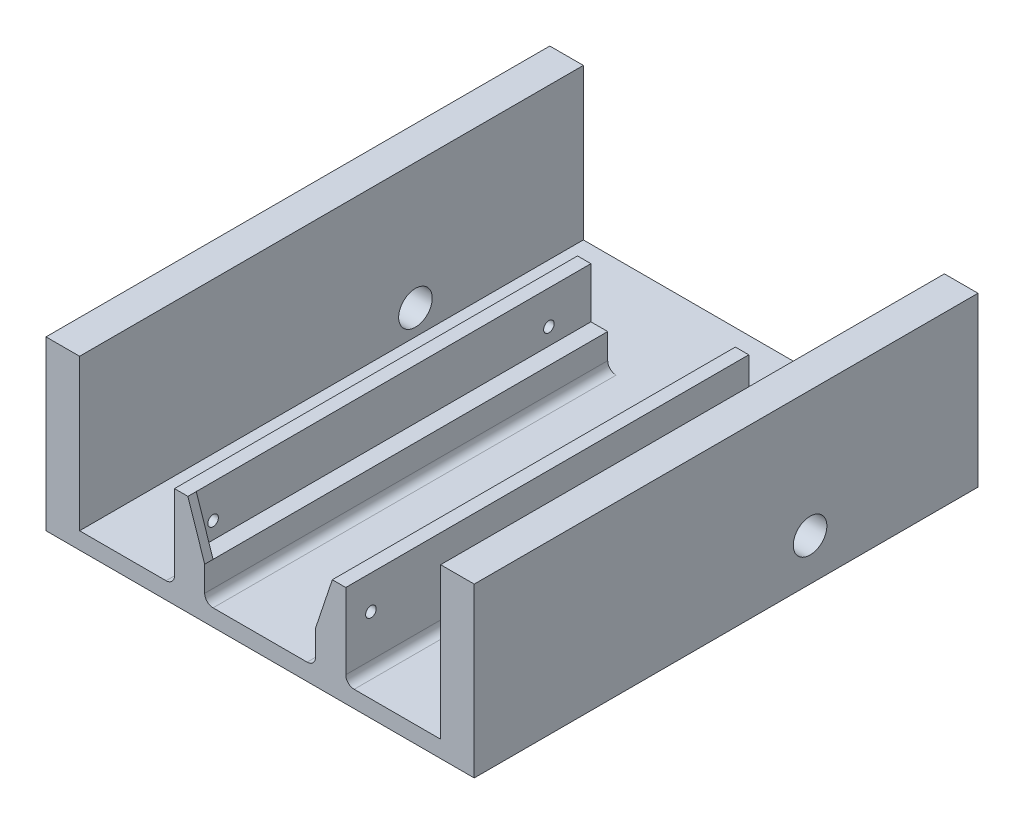
SolidWorks part; units mm, degrees
ref_plane "前基準面" through (0, 0, 0) normal (0, 0, 1) x (1, 0, 0)
ref_plane "上基準面" through (0, 0, 0) normal (0, 1, 0) x (1, 0, 0)
ref_plane "右基準面" through (0, 0, 0) normal (1, 0, 0) x (0, 0, -1)
sketch "草圖4" plane through (0, 0, 0) normal (0, 1, 0) x (1, 0, 0)
  line L1 (-127.5, 150) -> (127.5, 150)
  line L2 (-127.5, 150) -> (-127.5, -150)
  line L3 (-127.5, -150) -> (127.5, -150)
  line L4 (127.5, 150) -> (127.5, -150)
  line L5 (-127.5, 150) -> (127.5, -150) construction
  line L6 (-127.5, -150) -> (127.5, 150) construction
  point P0 (0, 0)
  dimension "D1" = 255
  dimension "D2" = 300
extrude "填料-伸長2" add sketch "草圖4" along normal blind 10
sketch "草圖7" plane through (0, 10, 0) normal (0, 1, 0) x (1, 0, 0)
  line L0 (-127.5, -150) -> (127.5, -150) construction
  line L1 (-127.5, 150) -> (-107.5, 150)
  line L2 (-127.5, 150) -> (-127.5, -150)
  line L3 (-127.5, -150) -> (-107.5, -150)
  line L4 (-107.5, 150) -> (-107.5, -150)
  line L5 (127.5, 150) -> (-127.5, 150) construction
  line L6 (127.5, -150) -> (107.5, -150)
  line L7 (127.5, -150) -> (127.5, 150)
  line L8 (127.5, 150) -> (107.5, 150)
  line L9 (107.5, -150) -> (107.5, 150)
  line L10 (0, 160.1697) -> (0, -166.2631) construction
  line L20 (42.5, -150) -> (-42.5, -150) construction
  line L21 (42.5, -150) -> (42.5, 110) construction
  line L22 (42.5, 110) -> (-42.5, 110) construction
  line L23 (-42.5, -150) -> (-42.5, 110) construction
  dimension "D1" = 20
  dimension "D2" = 20
  dimension "D4" = 260
  dimension "D5" = 85
extrude "填料-伸長3" add sketch "草圖7" along normal blind 90
sketch "草圖8" plane through (0, 0, 150) normal (0, 0, 1) x (1, 0, 0)
  line L0 (0, 114.0362) -> (0, -18.6102) construction
  line L1 (-33, 10) -> (-51, 10)
  line L2 (-107.5, 10) -> (107.5, 10) construction
  line L3 (-51, 10) -> (-51, 60)
  line L4 (-51, 60) -> (-43, 60)
  line L5 (-43, 60) -> (-43, 30)
  line L6 (-43, 30) -> (-33, 30)
  line L7 (-33, 30) -> (-33, 10)
  line L8 (43, 30) -> (33, 30)
  line L9 (43, 60) -> (43, 30)
  line L10 (51, 60) -> (43, 60)
  line L11 (51, 10) -> (51, 60)
  line L12 (33, 10) -> (51, 10)
  line L13 (33, 30) -> (33, 10)
  dimension "D1" = 43
  dimension "D2" = 8
  dimension "D3" = 10
  dimension "D4" = 20
  dimension "D5" = 50
  dimension "D6" = 66
extrude "填料-伸長4" add sketch "草圖8" against normal blind 240
sketch "草圖9" plane through (-127.5, 0, 0) normal (-1, 0, 0) x (0, 0, 1)
  line L0 (-150, 0) -> (150, 0) construction
  line L2 (-150, 100) -> (-150, 0) construction
  circle A0 centre (-50, 25) radius 10
  point P2 (-68.9466, 38.9013)
  point P5 (0, 0)
  point P7 (-150, 25.112)
  point P8 (-80.0453, -19.6192)
  dimension "D1" = 20
  dimension "D2" = 25
  dimension "D3" = 100
extrude "除料-伸長1" cut sketch "草圖9" against normal up to next
mirror "鏡射1" about plane through (0, 0, 0) normal (1, 0, 0) of "除料-伸長1"
sketch "草圖11" plane through (0, 0, 150) normal (0, 0, 1) x (1, 0, 0)
  line L0 (-43, 60) -> (-33, 30)
  line L1 (-51, 60) -> (-43, 60)
  line L2 (-51, 60) -> (-51, 10)
  line L3 (-51, 10) -> (-33, 10)
  line L4 (-33, 30) -> (-33, 10)
  line L5 (33, 10) -> (51, 10)
  line L6 (33, 10) -> (33, 30)
  line L7 (43, 60) -> (51, 60)
  line L8 (51, 10) -> (51, 60)
  line L9 (33, 30) -> (43, 60)
extrude "填料-伸長6" add sketch "草圖11" against normal blind 5
fillet "圓角1" radius 5 4 edges at (51, 10, 30) (-51, 10, 30) (33, 10, 30) (-33, 10, 30)
sketch "草圖12" plane through (51, 0, 0) normal (1, 0, 0) x (0, 0, -1)
  line L0 (-145, 60) -> (-145, 30) construction
  line L1 (-145, 60) -> (-145, 30) construction
  line L2 (-135, 40) -> (65, 40) construction
  line L3 (90, 30) -> (-145, 30) construction
  line L4 (-150, 60) -> (-150, 15)
  line L5 (-150, 15) -> (90, 15)
  line L6 (90, 15) -> (90, 60)
  line L7 (90, 60) -> (-150, 60)
  line L8 (-150, 60) -> (-150, 15)
  line L9 (-150, 15) -> (90, 15)
  line L10 (90, 15) -> (90, 60)
  line L11 (90, 60) -> (-150, 60)
  line L12 (90, 30) -> (-145, 30) construction
  circle A0 centre (-135, 40) radius 3.15
  circle A1 centre (65, 40) radius 3.15
  point P8 (65, 42.1921)
  dimension "D2" = 200
  dimension "D4" = 6.3
  dimension "D3" = 10
  dimension "D5" = 10
  dimension "D1" = 0
extrude "除料-伸長2" cut sketch "草圖12" against normal up to surface (102 mm away) contours A1 | A0 up to face at (-51, 37.5, 30)
